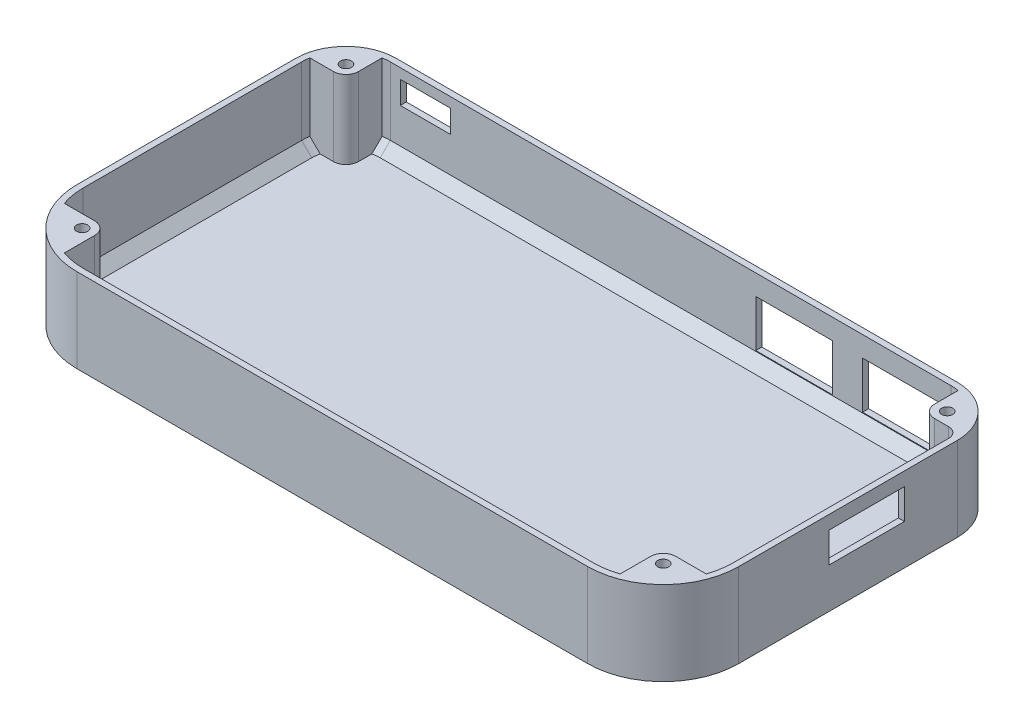
SolidWorks part; units mm, degrees
ref_plane "Plano frontal" through (0, 0, 0) normal (0, 0, 1) x (1, 0, 0)
ref_plane "Plano superior" through (0, 0, 0) normal (0, 1, 0) x (1, 0, 0)
ref_plane "Plano direito" through (0, 0, 0) normal (1, 0, 0) x (0, 0, -1)
sketch "Esboço1" plane through (0, 0, 0) normal (0, 1, 0) x (1, 0, 0)
  line L1 (-65.7, -34.2) -> (65.7, -34.2)
  line L2 (-65.7, -34.2) -> (-65.7, 34.2)
  line L3 (-65.7, 34.2) -> (65.7, 34.2)
  line L4 (65.7, -34.2) -> (65.7, 34.2)
  line L5 (-65.7, -34.2) -> (65.7, 34.2) construction
  line L6 (-65.7, 34.2) -> (65.7, -34.2) construction
  point P0 (0, 0)
  dimension "D1" = 131.4
  dimension "D2" = 68.4
extrude "Base" add sketch "Esboço1" along normal blind 1.2
fillet "Filete1" radius 15 1 edges at (65.7, 0.6, 34.2)
fillet "Filete2" radius 15 1 edges at (-65.7, 0.6, 34.2)
fillet "Filete3" radius 10 1 edges at (65.7, 0.6, -34.2)
fillet "Filete4" radius 10 1 edges at (-65.7, 0.6, -34.2)
sketch "Esboço5" plane through (0, 1.2, 0) normal (0, 1, 0) x (1, 0, 0)
  line L0 (55.7, 33) -> (-55.7, 33)
  line L1 (-64.5, 24.2) -> (-64.5, -19.2)
  line L2 (-50.7, -33) -> (50.7, -33)
  line L3 (64.5, -19.2) -> (64.5, 24.2)
  line L4 (55.7, 34.2) -> (-55.7, 34.2)
  line L5 (-65.7, 24.2) -> (-65.7, -19.2)
  line L6 (-50.7, -34.2) -> (50.7, -34.2)
  line L7 (65.7, -19.2) -> (65.7, 24.2)
  line L8 (55.7, 34.2) -> (-55.7, 34.2)
  line L9 (-65.7, 24.2) -> (-65.7, -19.2)
  line L10 (-50.7, -34.2) -> (50.7, -34.2)
  line L11 (65.7, -19.2) -> (65.7, 24.2)
  arc A0 (-55.7, 33) -> (-64.5, 24.2) centre (-55.7, 24.2) ccw
  arc A1 (-64.5, -19.2) -> (-50.7, -33) centre (-50.7, -19.2) ccw
  arc A2 (50.7, -33) -> (64.5, -19.2) centre (50.7, -19.2) ccw
  arc A3 (64.5, 24.2) -> (55.7, 33) centre (55.7, 24.2) ccw
  arc A4 (-55.7, 34.2) -> (-65.7, 24.2) centre (-55.7, 24.2) ccw
  arc A5 (-65.7, -19.2) -> (-50.7, -34.2) centre (-50.7, -19.2) ccw
  arc A6 (50.7, -34.2) -> (65.7, -19.2) centre (50.7, -19.2) ccw
  arc A7 (65.7, 24.2) -> (55.7, 34.2) centre (55.7, 24.2) ccw
  arc A8 (-55.7, 34.2) -> (-65.7, 24.2) centre (-55.7, 24.2) ccw
  arc A9 (-65.7, -19.2) -> (-50.7, -34.2) centre (-50.7, -19.2) ccw
  arc A10 (50.7, -34.2) -> (65.7, -19.2) centre (50.7, -19.2) ccw
  arc A11 (65.7, 24.2) -> (55.7, 34.2) centre (55.7, 24.2) ccw
  dimension "D1" = 0
extrude "Paredes" add sketch "Esboço5" along normal blind 15.5
sketch "Esboço6" plane through (0, 1.2, 0) normal (0, 1, 0) x (1, 0, 0)
  line L0 (65.7, -19.2) -> (65.7, 24.2) construction
  line L1 (-68.6453, 28.2) -> (71.5093, 28.2) construction
  line L2 (-69.9724, -26.2) -> (68.1989, -26.2) construction
  line L3 (-50.7, -34.2) -> (50.7, -34.2) construction
  line L4 (55.7, 34.2) -> (-55.7, 34.2) construction
  line L5 (-65.7, 24.2) -> (-65.7, -19.2) construction
  circle A0 centre (-59.7, 28.2) radius 2.5
  circle A1 centre (-57.7, -26.2) radius 2.5
  circle A2 centre (59.7, 28.2) radius 2.5
  circle A3 centre (57.7, -26.2) radius 2.5
  point P0 (0, 0)
  dimension "D1" = 8
  dimension "D2" = 5
  dimension "D3" = 8
  dimension "D4" = 6
  dimension "D5" = 6
  dimension "D6" = 5
  dimension "D7" = 6
  dimension "D8" = 6
  dimension "D9" = 8
  dimension "D10" = 8
extrude "Suporte dos parafusos" add sketch "Esboço6" along normal blind 15.5
sketch "Esboço7" plane through (0, 16.7, 0) normal (0, 1, 0) x (1, 0, 0)
  circle A0 centre (-59.7, 28.2) radius 1.1
  circle A1 centre (59.7, 28.2) radius 1.1
  circle A2 centre (57.7, -26.2) radius 1.1
  circle A3 centre (-57.7, -26.2) radius 1.1
  dimension "D1" = 2.2
extrude "Furo dos parafusos" cut sketch "Esboço7" against normal blind 6
sketch "Esboço23" plane through (0, 16.7, 0) normal (0, 1, 0) x (1, 0, 0)
  line L0 (57.2, 28.2) -> (57.2, 32.8712)
  line L1 (59.7, 25.7) -> (64.3712, 25.7)
  line L2 (59.7, 25.7) -> (62.2, 28.2)
  line L3 (62.2, 28.2) -> (59.7, 30.7)
  line L4 (59.7, 30.7) -> (57.2, 28.2)
  line L5 (-59.7, 25.7) -> (-64.3712, 25.7)
  line L6 (-57.2, 28.2) -> (-57.2, 32.8712)
  line L7 (-57.2, 28.2) -> (-59.7, 30.7)
  line L8 (-59.7, 30.7) -> (-62.2, 28.2)
  line L9 (-62.2, 28.2) -> (-59.7, 25.7)
  line L10 (57.7, -23.7) -> (63.7457, -23.7)
  line L11 (55.2, -26.2) -> (55.2, -32.2457)
  line L12 (57.7, -23.7) -> (60.2, -26.2)
  line L13 (60.2, -26.2) -> (57.7, -28.7)
  line L14 (57.7, -28.7) -> (55.2, -26.2)
  line L15 (-55.2, -26.2) -> (-55.2, -32.2457)
  line L16 (-57.7, -23.7) -> (-63.7457, -23.7)
  line L17 (-57.7, -23.7) -> (-60.2, -26.2)
  line L18 (-60.2, -26.2) -> (-57.7, -28.7)
  line L19 (-57.7, -28.7) -> (-55.2, -26.2)
  circle A0 centre (59.7, 28.2) radius 2.5 construction
  circle A1 centre (59.7, 28.2) radius 2.5 construction
  arc A2 (64.5, 24.2) -> (55.7, 33) centre (55.7, 24.2) ccw construction
  arc A3 (64.3712, 25.7) -> (57.2, 32.8712) centre (55.7, 24.2) ccw
  circle A4 centre (-59.7, 28.2) radius 2.5 construction
  circle A5 centre (-59.7, 28.2) radius 2.5 construction
  arc A7 (-55.7, 33) -> (-64.5, 24.2) centre (-55.7, 24.2) ccw construction
  arc A8 (-57.2, 32.8712) -> (-64.3712, 25.7) centre (-55.7, 24.2) ccw
  circle A9 centre (57.7, -26.2) radius 2.5 construction
  circle A10 centre (57.7, -26.2) radius 2.5 construction
  arc A11 (50.7, -33) -> (64.5, -19.2) centre (50.7, -19.2) ccw construction
  arc A12 (55.2, -32.2457) -> (63.7457, -23.7) centre (50.7, -19.2) ccw
  circle A13 centre (-57.7, -26.2) radius 2.5 construction
  circle A14 centre (-57.7, -26.2) radius 2.5 construction
  arc A15 (-64.5, -19.2) -> (-50.7, -33) centre (-50.7, -19.2) ccw construction
  arc A16 (-63.7457, -23.7) -> (-55.2, -32.2457) centre (-50.7, -19.2) ccw
extrude "Fechamentos" add sketch "Esboço23" against normal through all
sketch "Esboço14" plane through (0, 0, -34.2) normal (0, 0, -1) x (-1, 0, 0)
  line L1 (43.7, 14.7) -> (53.7, 14.7)
  line L2 (43.7, 14.7) -> (43.7, 10.2)
  line L3 (43.7, 10.2) -> (53.7, 10.2)
  line L4 (53.7, 14.7) -> (53.7, 10.2)
  line L5 (43.7, 14.7) -> (53.7, 10.2) construction
  line L6 (43.7, 10.2) -> (53.7, 14.7) construction
  line L7 (65.7, 16.7) -> (65.7, 0) construction
  line L9 (-55.7, 16.7) -> (55.7, 16.7) construction
  point P0 (48.7, 12.45)
  dimension "D1" = 2
  dimension "D2" = 10
  dimension "D3" = 4.5
  dimension "D4" = 17
extrude "Corte do USB" cut sketch "Esboço14" against normal blind 10
sketch "Esboço16" plane through (0, 0, -34.2) normal (0, 0, -1) x (-1, 0, 0)
  line L0 (-55.7, 0) -> (55.7, 0) construction
  line L1 (-53.3, 12.65) -> (-38.1, 12.65)
  line L2 (-53.3, 12.65) -> (-53.3, 3.35)
  line L3 (-53.3, 3.35) -> (-38.1, 3.35)
  line L4 (-38.1, 12.65) -> (-38.1, 3.35)
  line L5 (-53.3, 12.65) -> (-38.1, 3.35) construction
  line L6 (-53.3, 3.35) -> (-38.1, 12.65) construction
  line L7 (-32.1, 12.65) -> (-16.9, 12.65)
  line L8 (-32.1, 12.65) -> (-32.1, 3.35)
  line L9 (-32.1, 3.35) -> (-16.9, 3.35)
  line L10 (-16.9, 12.65) -> (-16.9, 3.35)
  line L11 (-32.1, 12.65) -> (-16.9, 3.35) construction
  line L12 (-32.1, 3.35) -> (-16.9, 12.65) construction
  line L13 (-65.7, 0) -> (-65.7, 16.7) construction
  point P0 (-45.7, 8)
  point P5 (-24.5, 8)
  dimension "D1" = 15.2
  dimension "D2" = 9.3
  dimension "D3" = 9.3
  dimension "D4" = 15.2
  dimension "D5" = 8
  dimension "D6" = 8
  dimension "D7" = 20
  dimension "D8" = 6
extrude "Corte das chaves" cut sketch "Esboço16" against normal blind 10
sketch "Esboço17" plane through (65.7, 0, 0) normal (1, 0, 0) x (0, 0, -1)
  line L0 (34.2, 16.7) -> (34.2, 0) construction
  line L1 (-1.3, 14) -> (13.7, 14)
  line L2 (-1.3, 14) -> (-1.3, 8)
  line L3 (-1.3, 8) -> (13.7, 8)
  line L4 (13.7, 14) -> (13.7, 8)
  line L5 (-1.3, 14) -> (13.7, 8) construction
  line L6 (-1.3, 8) -> (13.7, 14) construction
  line L10 (-19.2, 16.7) -> (24.2, 16.7) construction
  point P0 (6.2, 11)
  dimension "D1" = 28
  dimension "D2" = 15
  dimension "D3" = 6
  dimension "D4" = 2.7
extrude "Corte SD" cut sketch "Esboço17" against normal blind 10
chamfer "Chanfro base interior" distance 2 angle 45 12 edges at (-52.9814, 1.2, 32.8101) (52.9814, 1.2, 32.8101) (0, 1.2, 33) (64.3101, 1.2, 21.4814) (64.4677, 1.2, -24.9528) (64.5, 1.2, -2.5) (-64.4677, 1.2, -24.9528) (-64.3101, 1.2, 21.4814) (-64.5, 1.2, -2.5) (56.4528, 1.2, -32.9677) (-56.4528, 1.2, -32.9677) (0, 1.2, -33)
fillet "Filete5" radius 2 1 edges at (64.3712, 9.95, -25.7)
